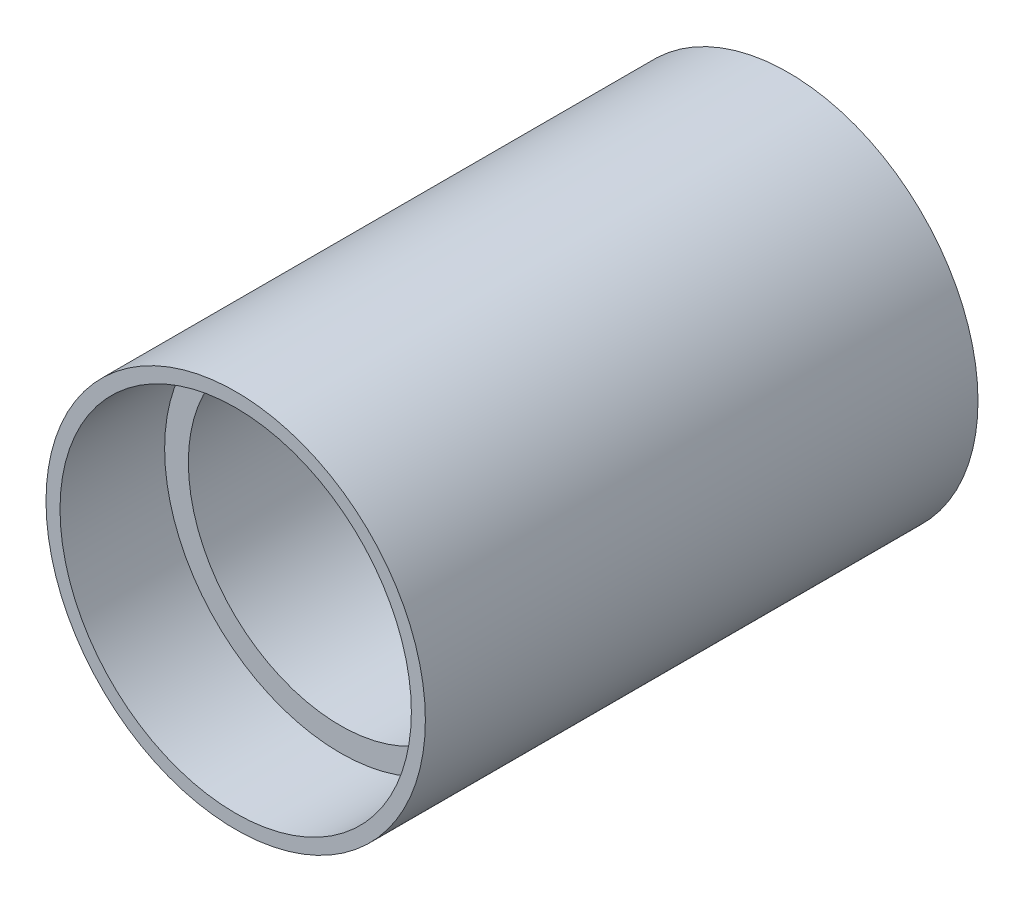
SolidWorks part; units mm, degrees
ref_plane "Top Plane" through (0, 0, 0) normal (0, 0, 1) x (1, 0, 0)
ref_plane "Front Plane" through (0, 0, 0) normal (0, 1, 0) x (1, 0, 0)
ref_plane "Right Plane" through (0, 0, 0) normal (1, 0, 0) x (0, 0, -1)
sketch "Profile Sketch" plane through (0, 0, 0) normal (0, 0, 1) x (1, 0, 0)
  circle A0 centre (0, 0) radius 12.7
  dimension "D1" = 25.4
extrude "Profile Extrude" add sketch "Profile Sketch" along normal blind 37
sketch "Bore Sketch" plane through (0, 0, 0) normal (0, 0, -1) x (-1, 0, 0)
  circle A0 centre (0, 0) radius 10.1745
  dimension "D1" = 20.349
extrude "Bore Cut" cut sketch "Bore Sketch" against normal through all
sketch "Bearing Pocket 1 Sketch" plane through (0, 0, 0) normal (0, 0, -1) x (-1, 0, 0)
  circle A1 centre (0, 0) radius 11.762
  dimension "D1" = 23.524
extrude "Bearing Pocket 1 Cut" cut sketch "Bearing Pocket 1 Sketch" against normal blind 7.005
sketch "Bearing Pocket 2 Sketch" plane through (0, 0, 37) normal (0, 0, 1) x (1, 0, 0)
  circle A0 centre (0, 0) radius 11.762
  dimension "D1" = 23.524
extrude "Bearing Pocket 2 Cut" cut sketch "Bearing Pocket 2 Sketch" against normal blind 7.005
equation "\"bearing_pocket_diameter\"=0.926142"
equation "\"D1@Bearing Pocket 1 Sketch\"=\"bearing_pocket_diameter\""
equation "\"bearing_pocket_depth\"=0.275787"
equation "\"D1@Bearing Pocket 1 Cut\"=\"bearing_pocket_depth\""
equation "\"D1@Bearing Pocket 2 Sketch\"=\"bearing_pocket_diameter\""
equation "\"D1@Bearing Pocket 2 Cut\"=\"bearing_pocket_depth\""
equation "\"D1@Bore Sketch\"=\"bearing_pocket_diameter\"-0.125"
